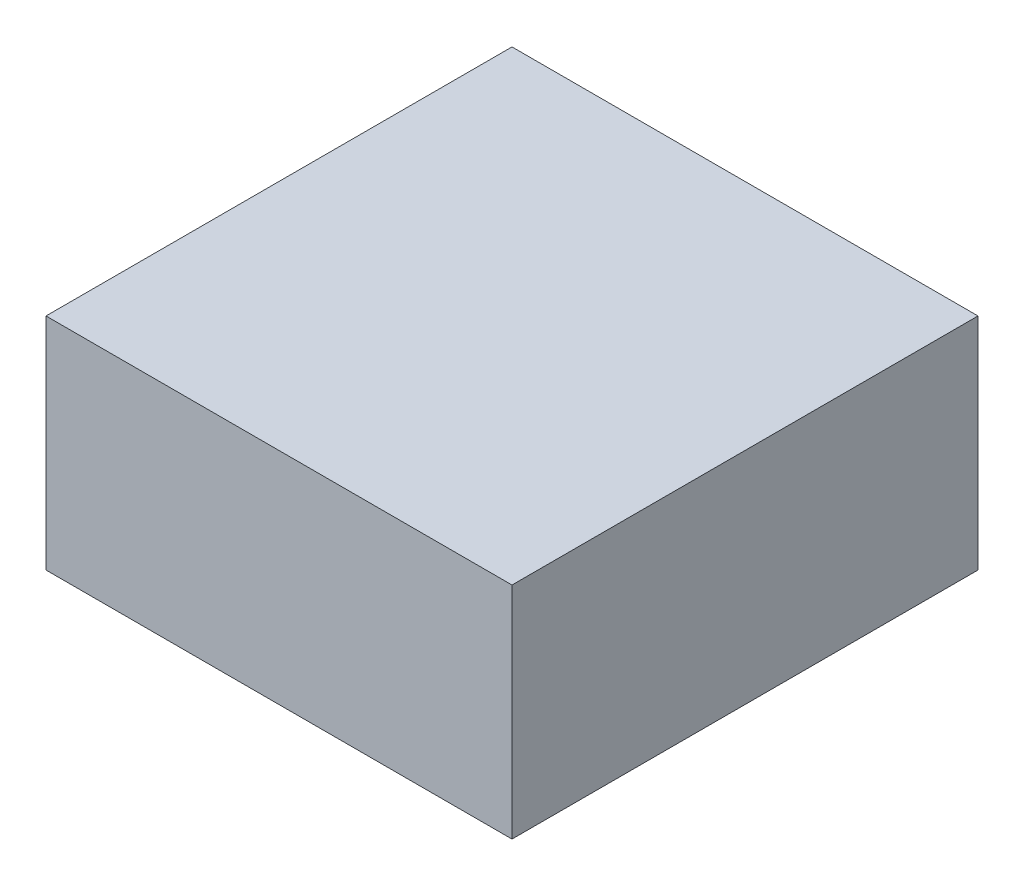
SolidWorks part; units mm, degrees
ref_plane "Front Plane" through (0, 0, 0) normal (0, 0, 1) x (1, 0, 0)
ref_plane "Top Plane" through (0, 0, 0) normal (0, 1, 0) x (1, 0, 0)
ref_plane "Right Plane" through (0, 0, 0) normal (1, 0, 0) x (0, 0, -1)
sketch "Sketch1" plane through (0, 0, 0) normal (0, 1, 0) x (1, 0, 0)
  line L1 (0, 0) -> (18, 0)
  line L2 (0, 0) -> (0, 18)
  line L3 (0, 18) -> (18, 18)
  line L4 (18, 0) -> (18, 18)
  dimension "D1" = 18
extrude "Boss-Extrude1" add sketch "Sketch1" along normal blind 8.5
